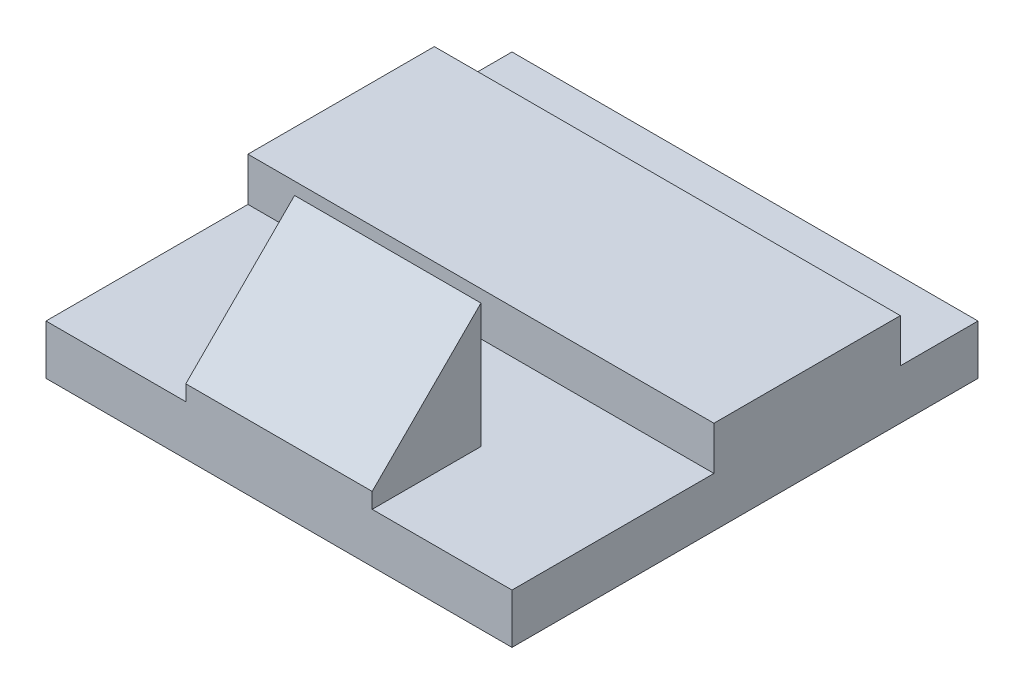
SolidWorks part; units mm, degrees
ref_plane "Front Plane" through (0, 0, 0) normal (0, 0, 1) x (1, 0, 0)
ref_plane "Top Plane" through (0, 0, 0) normal (0, 1, 0) x (1, 0, 0)
ref_plane "Right Plane" through (0, 0, 0) normal (1, 0, 0) x (0, 0, -1)
sketch "Sketch1" plane through (0, 0, 0) normal (0, 1, 0) x (1, 0, 0)
  line L1 (-150, 150) -> (150, 150)
  line L2 (-150, 150) -> (-150, -150)
  line L3 (-150, -150) -> (150, -150)
  line L4 (150, 150) -> (150, -150)
  dimension "D1" = 300
  dimension "D2" = 300
  dimension "D3" = 150
  dimension "D4" = 150
extrude "Boss-Extrude1" add sketch "Sketch1" along normal blind 32
sketch "Sketch2" plane through (0, 32, 0) normal (0, 1, 0) x (1, 0, 0)
  line L0 (-150, 150) -> (-150, -150) construction
  line L1 (-150, 100) -> (150, 100)
  line L2 (-150, 100) -> (-150, -20)
  line L3 (-150, -20) -> (150, -20)
  line L4 (150, 100) -> (150, -20)
  line L5 (150, -150) -> (150, 150) construction
  line L6 (150, 150) -> (-150, 150) construction
  dimension "D1" = 120
  dimension "D2" = 50
extrude "Boss-Extrude2" add sketch "Sketch2" along normal blind 28
sketch "Sketch3" plane through (0, 32, 0) normal (0, 1, 0) x (1, 0, 0)
  line L0 (-150, -150) -> (150, -150) construction
  line L1 (-60, -150) -> (60, -150)
  line L2 (-60, -150) -> (-60, -80)
  line L3 (-60, -80) -> (60, -80)
  line L4 (60, -150) -> (60, -80)
  line L5 (150, -150) -> (150, -20) construction
  dimension "D1" = 120
  dimension "D2" = 70
  dimension "D3" = 90
extrude "Boss-Extrude3" add sketch "Sketch3" along normal blind 80
sketch "Sketch4" plane through (60, 0, 0) normal (1, 0, 0) x (0, 0, -1)
  line L5 (-80, 112) -> (-150, 42)
  line L6 (-150, 112) -> (-150, 32) construction
  line L7 (-150, 42) -> (-150, 112)
  line L8 (-150, 112) -> (-80, 112)
  dimension "D1" = 45
extrude "Cut-Extrude1" cut sketch "Sketch4" against normal blind 120
sketch "wheel_left" plane through (-150, 0, 0) normal (-1, 0, 0) x (0, 0, 1)
  line L0 (-150, 32) -> (-150, 0) construction
  line L1 (150, 32) -> (150, 0) construction
  line L2 (-150, 0) -> (150, 0) construction
  point P0 (-120, 16.2)
  point P1 (0, 16.2)
  point P2 (120, 16.2)
  point P9 (0, 0)
  dimension "D1" = 30
  dimension "D2" = 150
  dimension "D3" = 30
  dimension "D4" = 16.2
  dimension "D5" = 16.2
  dimension "D6" = 16.2
sketch "wheel_right" plane through (150, 0, 0) normal (1, 0, 0) x (0, 0, -1)
  line L0 (-150, 32) -> (-150, 0) construction
  line L1 (150, 32) -> (150, 0) construction
  line L2 (-150, 0) -> (150, 0) construction
  point P0 (-120, 16)
  point P1 (0, 16)
  point P2 (120, 16)
  point P9 (0, 0)
  point P10 (0, 0)
  dimension "D1" = 30
  dimension "D2" = 150
  dimension "D3" = 30
  dimension "D4" = 16
  dimension "D5" = 16
  dimension "D6" = 16
sketch "arm_mounts" plane through (0, 60, 0) normal (0, 1, 0) x (1, 0, 0)
  line L0 (-150, -20) -> (150, -20) construction
  line L1 (-150, 100) -> (-150, -20) construction
  line L2 (150, -20) -> (150, 100) construction
  point P0 (-85, 40)
  point P1 (85, 40)
  dimension "D1" = 60
  dimension "D2" = 60
  dimension "D3" = 65
  dimension "D4" = 65
ref_axis "Axis1" through (-150, 16.2, -120) along (-1, 0, 0)
ref_axis "Axis2" through (-150, 16.2, 0) along (-1, 0, 0)
ref_axis "Axis3" through (-150, 16.2, 120) along (-1, 0, 0)
ref_axis "Axis4" through (150, 16, -120) along (1, 0, 0)
ref_axis "Axis5" through (150, 16, 0) along (1, 0, 0)
ref_axis "Axis6" through (150, 16, 120) along (1, 0, 0)
ref_axis "Axis7" through (-85, 60, -40) along (0, 1, 0)
ref_axis "Axis8" through (85, 60, -40) along (0, 1, 0)
